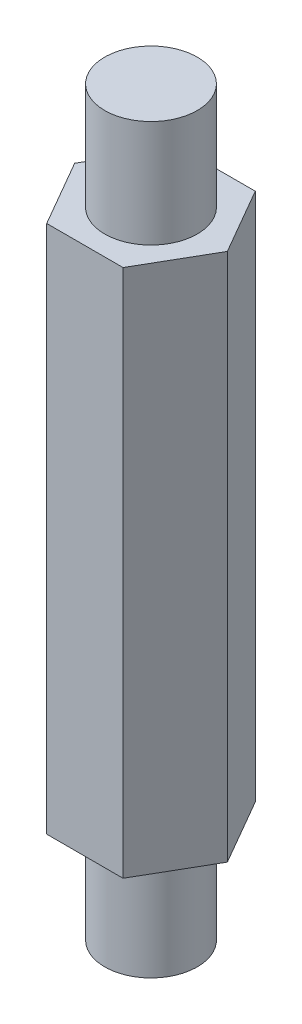
SolidWorks part; units mm, degrees
ref_plane "Front Plane" through (0, 0, 0) normal (0, 0, 1) x (1, 0, 0)
ref_plane "Top Plane" through (0, 0, 0) normal (0, 1, 0) x (1, 0, 0)
ref_plane "Right Plane" through (0, 0, 0) normal (1, 0, 0) x (0, 0, -1)
sketch "Sketch3" plane through (0, 0, 0) normal (0, 1, 0) x (1, 0, 0)
  line L1 (-5.7735, 0) -> (-2.8868, -5)
  line L2 (-2.8868, -5) -> (2.8868, -5)
  line L3 (2.8868, -5) -> (5.7735, 0)
  line L4 (5.7735, 0) -> (2.8868, 5)
  line L5 (2.8868, 5) -> (-2.8868, 5)
  line L6 (-2.8868, 5) -> (-5.7735, 0)
  circle A0 centre (0, 0) radius 5 construction
  dimension "D1" = 10
extrude "Boss-Extrude1" add sketch "Sketch3" along normal blind 40
sketch "Sketch5" plane through (0, 40, 0) normal (0, 1, 0) x (1, 0, 0)
  circle A0 centre (0, 0) radius 3.5
  dimension "D1" = 7
extrude "Boss-Extrude2" add sketch "Sketch5" along normal blind 8.0916
extrude "Boss-Extrude3" add sketch "Sketch5<2>" along normal blind 8
sketch "Sketch5<2>" plane through (0, 40, 0) normal (0, 1, 0) x (1, 0, 0) same geometry as "Sketch5"
sketch "Sketch9" plane through (0, 0, 0) normal (0, -1, 0) x (1, 0, 0)
  circle A0 centre (0, 0) radius 3.5
  dimension "D1" = 7
extrude "Boss-Extrude6" add sketch "Sketch9" along normal blind 8 contours A0
